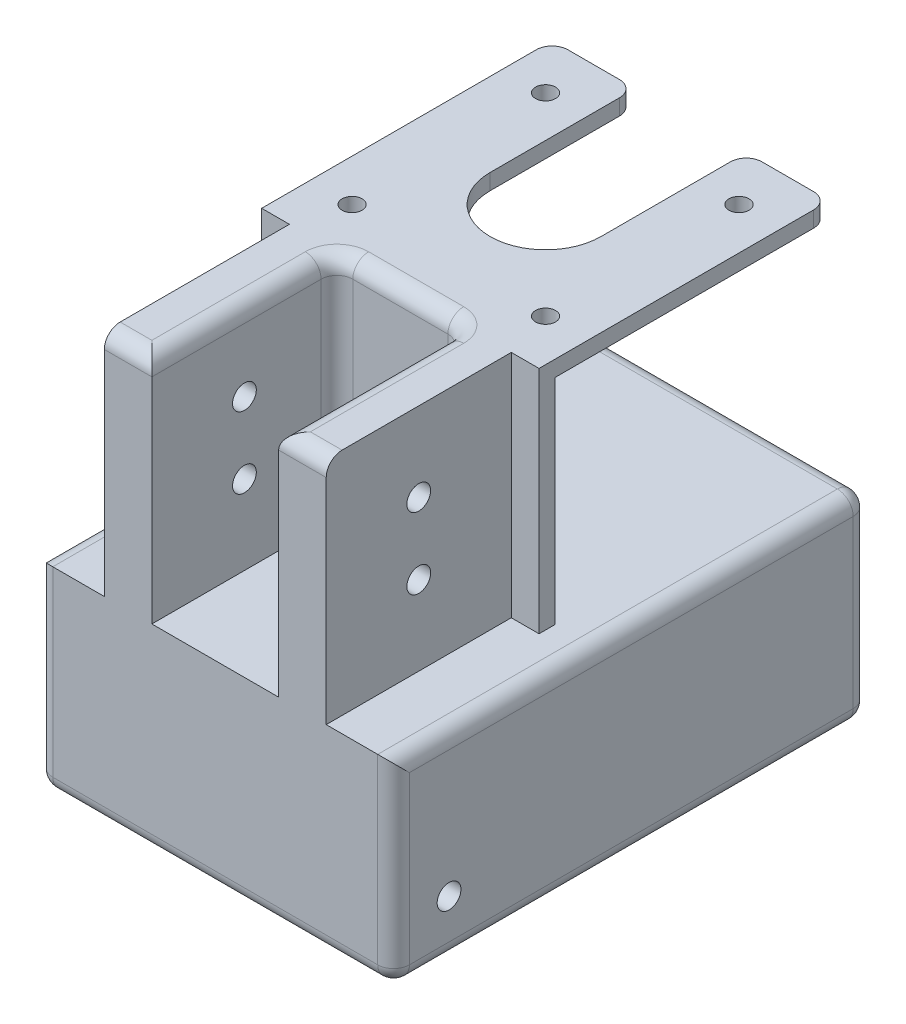
SolidWorks part; units mm, degrees
ref_plane "Front Plane" through (0, 0, 0) normal (0, 0, 1) x (1, 0, 0)
ref_plane "Top Plane" through (0, 0, 0) normal (0, 1, 0) x (1, 0, 0)
ref_plane "Right Plane" through (0, 0, 0) normal (1, 0, 0) x (0, 0, -1)
sketch "Sketch3" plane through (0, 0, 0) normal (0, 1, 0) x (-1, 0, 0)
  line L1 (0, 0) -> (57.15, 0)
  line L2 (0, 0) -> (0, 76.2)
  line L3 (0, 76.2) -> (57.15, 76.2)
  line L4 (57.15, 0) -> (57.15, 76.2)
  dimension "D1" = 76.2
  dimension "D2" = 57.15
extrude "Boss-Extrude2" add sketch "Sketch3" against normal blind 31.75
sketch "Sketch4" plane through (0, -31.75, 0) normal (0, -1, 0) x (1, 0, 0)
  line L1 (-3.81, 72.39) -> (-53.34, 72.39)
  line L2 (-3.81, 72.39) -> (-3.81, 3.81)
  line L3 (-3.81, 3.81) -> (-53.34, 3.81)
  line L4 (-53.34, 72.39) -> (-53.34, 3.81)
  line L8 (-57.15, 76.2) -> (0, 76.2) construction
  line L9 (0, 0) -> (-57.15, 0) construction
  line L10 (0, 76.2) -> (0, 0) construction
  line L11 (-57.15, 0) -> (-57.15, 76.2) construction
  dimension "D1" = 3.81
  dimension "D2" = 3.81
  dimension "D3" = 3.81
  dimension "D4" = 3.81
extrude "Cut-Extrude2" cut sketch "Sketch4" against normal offset from surface (26.67 mm away) 5.08 up to face at (-28.575, 0, 38.1)
sketch "Sketch5" plane through (-57.15, 0, 0) normal (1, 0, 0) x (0, 0, -1)
  line L1 (-14.478, -27.94) -> (-5.08, -27.94)
  line L2 (-14.478, -27.94) -> (-14.478, -16.51)
  line L3 (-14.478, -16.51) -> (-5.08, -16.51)
  line L4 (-5.08, -27.94) -> (-5.08, -16.51)
  line L6 (0, -31.75) -> (0, 0) construction
  line L7 (0, -31.75) -> (-76.2, -31.75) construction
  dimension "D1" = 5.08
  dimension "D2" = 3.81
  dimension "D3" = 11.43
  dimension "D4" = 9.398
extrude "Power Hole" cut sketch "Sketch5" along normal up to next
sketch "Sketch6" plane through (-57.15, 0, 0) normal (-1, 0, 0) x (0, 0, 1)
  line L0 (46.54, 0) -> (46.54, 36.83)
  line L1 (46.54, 36.83) -> (0, 36.83)
  line L2 (0, 36.83) -> (0, 34.29)
  line L3 (0, 34.29) -> (44, 34.29)
  line L4 (44, 34.29) -> (44, 0)
  line L5 (0, 0) -> (76.2, 0) construction
  line L6 (44, 0) -> (46.54, 0)
  line L7 (0, -31.75) -> (0, 0) construction
  dimension "D1" = 44
  dimension "D2" = 34.29
  dimension "D3" = 2.54
  dimension "D4" = 2.54
extrude "Motor Mounting Shape" add sketch "Sketch6" against normal up to surface (57.15 mm away) up to face at (0, -15.875, 38.1)
sketch "Sketch8" plane through (0, 36.83, 0) normal (0, 1, 0) x (1, 0, 0)
  line L0 (-44.075, -38.77) -> (-13.075, -7.77) construction
  line L1 (-13.075, -38.77) -> (-44.075, -7.77) construction
  line L2 (-44.075, -38.77) -> (-44.075, -7.77) construction
  line L3 (-44.075, -7.77) -> (-13.075, -7.77) construction
  line L4 (-28.575, -46.54) -> (-28.575, 0) construction
  line L5 (0, -46.54) -> (-57.15, -46.54) construction
  line L6 (0, 0) -> (-57.15, 0) construction
  line L7 (-37.465, 0) -> (-19.685, 0)
  line L8 (-19.685, 0) -> (-19.685, -23.27)
  line L9 (-37.465, -23.27) -> (-37.465, 0)
  circle A1 centre (-44.075, -7.77) radius 1.6
  circle A2 centre (-13.075, -7.77) radius 1.6
  circle A3 centre (-13.075, -38.77) radius 1.6
  circle A4 centre (-44.075, -38.77) radius 1.6
  arc A6 (-37.465, -23.27) -> (-19.685, -23.27) centre (-28.575, -23.27) ccw
  point P10 (-28.575, -23.27)
  dimension "D2" = 3.2
  dimension "D3" = 8.89
  dimension "D1" = 31
extrude "Motor-Mounting-Holes" cut sketch "Sketch8" against normal up to next
sketch "Sketch7" plane through (0, 0, 0) normal (0, 1, 0) x (1, 0, 0)
  line L0 (-46.355, -76.2) -> (-46.355, -46.54)
  line L1 (-57.15, -76.2) -> (0, -76.2) construction
  line L2 (-46.355, -46.54) -> (-38.735, -46.54)
  line L3 (-38.735, -46.54) -> (-38.735, -76.2)
  line L4 (-38.735, -76.2) -> (-46.355, -76.2)
  line L5 (-18.415, -76.2) -> (-10.795, -76.2)
  line L6 (-10.795, -76.2) -> (-10.795, -46.54)
  line L7 (-10.795, -46.54) -> (-18.415, -46.54)
  line L8 (-18.415, -46.54) -> (-18.415, -76.2)
  line L9 (-46.355, -76.2) -> (-57.15, -76.2) construction
  line L10 (-38.735, -76.2) -> (-18.415, -76.2) construction
  line L11 (-10.795, -76.2) -> (0, -76.2) construction
  line L12 (0, -46.54) -> (-57.15, -46.54) construction
  dimension "D1" = 7.62
  dimension "D2" = 20.32
extrude "Tray Support Mounting Shape" add sketch "Sketch7" along normal up to surface (36.83 mm away) up to face at (-44.075, 36.83, 40.37)
sketch "Sketch9" plane through (0, -5.08, 0) normal (0, -1, 0) x (1, 0, 0)
  line L0 (-38.735, 76.2) -> (-38.735, 46.54) construction
  line L1 (-38.735, 51.62) -> (-18.415, 51.62)
  line L2 (-38.735, 51.62) -> (-38.735, 38.92)
  line L3 (-38.735, 38.92) -> (-18.415, 38.92)
  line L4 (-18.415, 51.62) -> (-18.415, 38.92)
  line L5 (-18.415, 46.54) -> (-18.415, 76.2) construction
  line L6 (-18.415, 46.54) -> (-38.735, 46.54) construction
  line L7 (0, 44) -> (-57.15, 44) construction
  point P4 (-37.0595, 52.0602)
  dimension "D1" = 5.08
  dimension "D2" = 5.08
extrude "Cut-Extrude3" cut sketch "Sketch9" against normal blind 16.51
sketch "Sketch10" plane through (0, 36.83, 0) normal (0, 1, 0) x (1, 0, 0)
  line L0 (-46.355, -46.54) -> (-57.15, -46.54) construction
  line L1 (-57.15, 0) -> (-50.8, 0)
  line L2 (-57.15, 0) -> (-57.15, -46.54)
  line L3 (-57.15, -46.54) -> (-50.8, -46.54)
  line L4 (-50.8, 0) -> (-50.8, -46.54)
  line L5 (0, -46.54) -> (-10.795, -46.54) construction
  line L6 (0, 0) -> (-6.35, 0)
  line L7 (0, 0) -> (0, -46.54)
  line L8 (0, -46.54) -> (-6.35, -46.54)
  line L9 (-6.35, 0) -> (-6.35, -46.54)
  dimension "D1" = 6.35
extrude "Cut-Extrude4" cut sketch "Sketch10" against normal up to surface (36.83 mm away) up to face at (-28.575, 0, 31.73)
sketch "Sketch11" plane through (-46.355, 0, 0) normal (-1, 0, 0) x (0, 0, 1)
  line L0 (61.37, 36.83) -> (61.37, 0) construction
  line L1 (46.54, 36.83) -> (76.2, 36.83) construction
  line L2 (46.54, 0) -> (76.2, 0) construction
  circle A0 centre (61.37, 24.13) radius 1.905
  circle A1 centre (61.37, 12.7) radius 1.905
  point P10 (61.37, 24.601)
  point P11 (61.37, 8.6604)
  dimension "D1" = 3.81
  dimension "D2" = 12.7
  dimension "D3" = 12.7
  dimension "D4" = 11.43
extrude "Cut-Extrude5" cut sketch "Sketch11" against normal through all
sketch "Sketch12" plane through (0, 0, 0) normal (1, 0, 0) x (0, 0, -1)
  line L2 (-76.2, -31.75) -> (-76.2, 0) construction
  line L3 (-76.2, -31.75) -> (0, -31.75) construction
  circle A0 centre (-67.31, -22.86) radius 1.905
  dimension "D3" = 3.81
  dimension "D1" = 8.89
  dimension "D2" = 8.89
extrude "BigButtonWireHole" cut sketch "Sketch12" against normal up to next
sketch "Sketch13" plane through (-38.735, 0, 0) normal (1, 0, 0) x (0, 0, -1)
  line L0 (-46.54, 11.43) -> (-46.54, 15.24)
  line L1 (-46.54, 36.83) -> (-46.54, 11.43) construction
  line L3 (-55.43, 6.35) -> (-55.43, 0)
  line L4 (-76.2, 0) -> (-51.62, 0) construction
  line L5 (-55.43, 0) -> (-51.62, 0)
  line L6 (-51.62, 0) -> (-51.62, 6.35)
  arc A0 (-46.54, 11.43) -> (-51.62, 6.35) centre (-46.54, 6.35) ccw
  arc A1 (-55.43, 6.35) -> (-46.54, 15.24) centre (-46.54, 6.35) cw
  point P4 (-46.0452, 5.8683)
  dimension "D1" = 3.81
  dimension "D2" = 3.81
extrude "Boss-Extrude3" add sketch "Sketch13" along normal up to surface (20.32 mm away) up to face at (-18.415, 24.13, 59.465)
fillet "Fillet2" radius 2.54 14 edges at (-38.735, -5.08, 45.27) (-18.415, -5.08, 45.27) (-38.735, 9.9421, 50.1321) (-18.415, 9.9421, 50.1321) (-38.735, 0.635, 51.62) (-28.575, -5.08, 51.62) (-18.415, 0.635, 51.62) (-28.575, -5.08, 38.92) (-38.735, 0, 41.46) (-28.575, 0, 38.92) (-18.415, 0, 41.46) (-38.735, 5.715, 44) (-28.575, 11.43, 44) (-18.415, 5.715, 44)
fillet "Fillet1" radius 2.54 23 edges at (0, -31.75, 38.1) (-28.575, -31.75, 0) (-57.15, -31.75, 38.1) (-28.575, -31.75, 76.2) (-57.15, 0, 38.1) (0, 0, 38.1) (-28.575, 0, 0) (-57.15, -15.875, 76.2) (-57.15, -15.875, 0) (0, -15.875, 76.2) (0, -15.875, 0) (-6.35, 35.56, 0) (-19.685, 35.56, 0) (-37.465, 35.56, 0) (-50.8, 35.56, 0) (-18.415, 36.83, 61.37) (-38.735, 36.83, 61.37) (-28.575, 36.83, 46.54) (-18.415, 26.035, 46.54) (-28.575, 15.24, 46.54) (-38.735, 26.035, 46.54) (-14.605, 36.83, 76.2) (-42.545, 36.83, 76.2)
